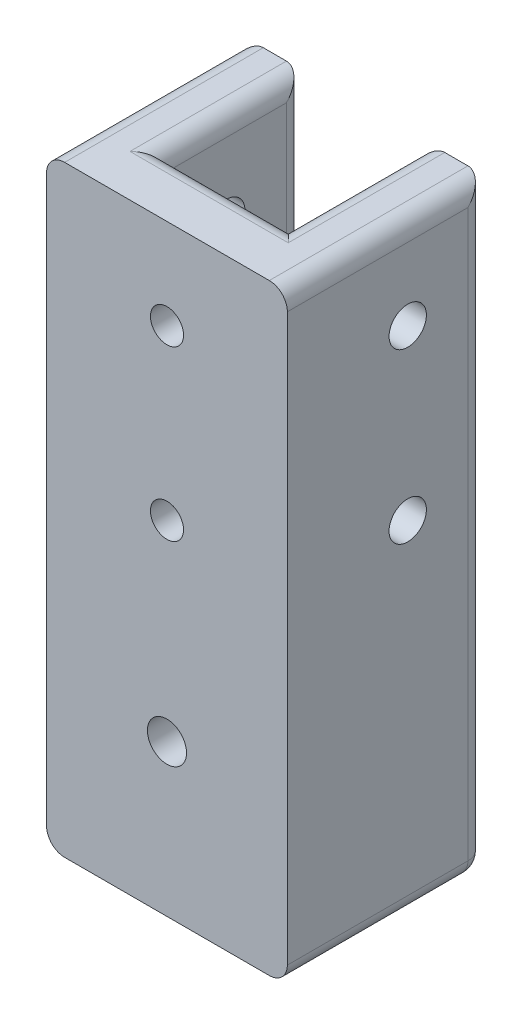
SolidWorks part; units mm, degrees
ref_plane "Front Plane" through (0, 0, 0) normal (0, 0, 1) x (1, 0, 0)
ref_plane "Top Plane" through (0, 0, 0) normal (0, 1, 0) x (1, 0, 0)
ref_plane "Right Plane" through (0, 0, 0) normal (1, 0, 0) x (0, 0, -1)
sketch "Sketch1" plane through (0, 0, 0) normal (0, 0, 1) x (1, 0, 0)
  line L1 (0, 0) -> (40, 0)
  line L2 (0, 0) -> (0, 100)
  line L3 (0, 100) -> (40, 100)
  line L4 (40, 0) -> (40, 100)
  line L5 (22.975, 25.15) -> (17.025, 25.15)
  line L6 (22.975, 25.15) -> (22.975, 37.8)
  line L7 (22.975, 37.8) -> (17.025, 37.8)
  line L8 (17.025, 25.15) -> (17.025, 37.8)
  circle A0 centre (20, 25.15) radius 10.15
  circle A1 centre (20, 25.15) radius 2.75
  point P11 (20, 25.15)
  point P14 (20, 0)
  dimension "D1" = 20.3
  dimension "D7" = 5.5
  dimension "D2" = 5.95
  dimension "D3" = 22.8
  dimension "D4" = 15
  dimension "D5" = 40
  dimension "D6" = 100
extrude "Boss-Extrude1" add sketch "Sketch1" along normal blind 25 contours L1 L4 L3 L2 A0 L8 L7 L6 region at (20, 52.2553, 0)
extrude "Boss-Extrude2" add sketch "Sketch1<3>" along normal blind 8 from surface contours L1 L4 L3 L2 A0 L8 L7 L6 | L8 A0 L6 L5 | L6 A0 L8 L5 | A0 L6 L7 L8 region at (20, 52.2553, 0) region at (23.259, 30.0021, 0) region at (20, 31.1086, 0) region at (20, 36.4731, 0) starting at face at (20, 31.3636, 25)
sketch "Sketch1<3>" plane through (0, 0, 0) normal (0, 0, 1) x (1, 0, 0) same geometry as "Sketch1"
sketch "Sketch2" plane through (0, 0, 0) normal (0, -1, 0) x (1, 0, 0)
  line L0 (0, 0) -> (40, 0) construction
  line L1 (9.85, 0) -> (30.15, 0)
  line L2 (9.85, 0) -> (9.85, 23)
  line L3 (9.85, 23) -> (30.15, 23)
  line L4 (30.15, 0) -> (30.15, 23)
  line L5 (40, 33) -> (0, 33) construction
  point P8 (20, 33)
  point P9 (20, 23)
  dimension "D1" = 20.3
  dimension "D2" = 10
extrude "Cut-Extrude1" cut sketch "Sketch2" against normal through all from offset 50 offset against normal yes
sketch "Sketch3" plane through (30.15, 0, 0) normal (-1, 0, 0) x (0, 0, 1)
  line L0 (23, 100) -> (23, 50) construction
  line L1 (0, 50) -> (23, 50) construction
  line L2 (0, 100) -> (23, 100) construction
  circle A0 centre (13, 57) radius 3.1
  circle A1 centre (13, 85) radius 3.1
  dimension "D5" = 6.2
  dimension "D6" = 6.2
  dimension "D1" = 10
  dimension "D2" = 10
  dimension "D3" = 7
  dimension "D4" = 15
extrude "Cut-Extrude2" cut sketch "Sketch3" against normal through all both and the other way through all
sketch "Sketch4" plane through (0, 0, 23) normal (0, 0, -1) x (-1, 0, 0)
  line L0 (-30.15, 100) -> (-9.85, 100) construction
  line L1 (-30.15, 50) -> (-9.85, 50) construction
  circle A0 centre (-20, 57) radius 2.75
  circle A1 centre (-20, 85) radius 2.75
  point P9 (-20, 50)
  dimension "D3" = 5.5
  dimension "D4" = 5.5
  dimension "D1" = 15
  dimension "D2" = 7
extrude "Cut-Extrude3" cut sketch "Sketch4" against normal through all
fillet "Fillet1" radius 3 13 edges at (40, 0, 16.5) (0, 0, 16.5) (0, 100, 16.5) (40, 100, 16.5) (20, 50, 0) (20, 0, 0) (40, 50, 0) (0, 50, 0) (30.15, 75, 0) (9.85, 75, 0) (9.85, 100, 11.5) (30.15, 100, 11.5) (20, 100, 23)
fillet "Fillet2" radius 1 4 edges at (22.975, 36.3271, 0) (20, 37.8, 0) (17.025, 36.3271, 0) (20, 15, 0)
sketch "Sketch6" plane through (0, 0, 25) normal (0, 0, -1) x (-1, 0, 0)
  circle A0 centre (-20, 25.15) radius 3.25
  dimension "D1" = 6.5
extrude "Cut-Extrude4" cut sketch "Sketch6" against normal through all
